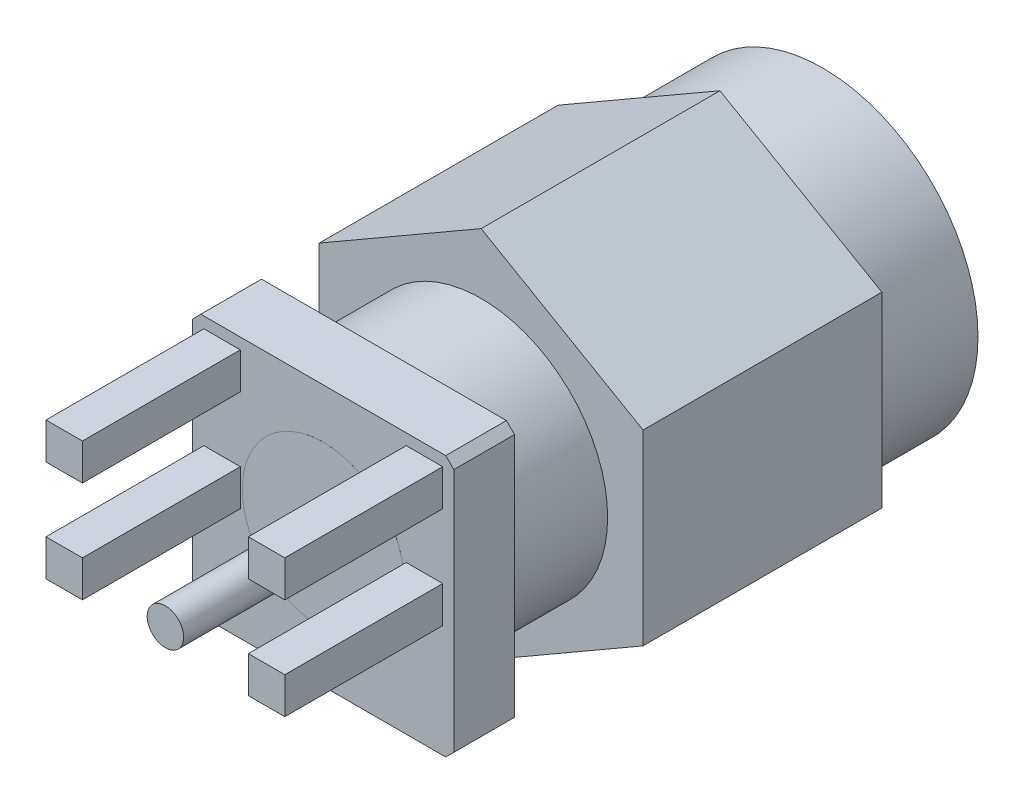
SolidWorks part; units mm, degrees
ref_plane "Спереди" through (0, 0, 0) normal (0, 0, 1) x (1, 0, 0)
ref_plane "Сверху" through (0, 0, 0) normal (0, 1, 0) x (1, 0, 0)
ref_plane "Справа" through (0, 0, 0) normal (1, 0, 0) x (0, 0, -1)
sketch "Эскиз1" plane through (0, 0, 0) normal (0, 0, 1) x (1, 0, 0)
  line L0 (3.225, 2.95) -> (-3.225, 2.95) construction
  line L1 (3.225, -3.225) -> (-3.225, -3.225)
  line L2 (3.225, -3.225) -> (3.225, 3.225)
  line L3 (3.225, 3.225) -> (-3.225, 3.225)
  line L4 (-3.225, -3.225) -> (-3.225, 3.225)
  line L5 (3.225, -3.225) -> (-3.225, 3.225) construction
  line L6 (3.225, 3.225) -> (-3.225, -3.225) construction
  line L7 (-2.95, 3.225) -> (-2.95, -3.225) construction
  line L8 (2.95, 3.225) -> (2.95, -3.225) construction
  line L9 (-2.95, 2.95) -> (-2.05, 2.95)
  line L13 (-3.225, 2.05) -> (3.225, 2.05) construction
  line L14 (-3.225, 0.45) -> (3.225, 0.45) construction
  line L15 (-3.225, -0.45) -> (3.225, -0.45) construction
  line L16 (-2.05, 2.05) -> (-2.95, 2.05)
  line L17 (-2.95, 2.05) -> (-2.95, 2.95)
  line L18 (-2.05, 2.95) -> (-2.05, 2.05)
  line L19 (-2.05, 3.225) -> (-2.05, -3.225) construction
  line L20 (2.95, 2.95) -> (2.05, 2.95)
  line L21 (2.95, 2.95) -> (2.95, 2.05)
  line L22 (2.95, 2.05) -> (2.05, 2.05)
  line L23 (2.05, 2.95) -> (2.05, 2.05)
  line L24 (2.05, 3.225) -> (2.05, -3.225) construction
  line L26 (-2.05, 0.45) -> (-2.95, 0.45)
  line L27 (-2.05, 0.45) -> (-2.05, -0.45)
  line L28 (-2.05, -0.45) -> (-2.95, -0.45)
  line L29 (-2.95, 0.45) -> (-2.95, -0.45)
  line L30 (2.05, 0.45) -> (2.95, 0.45)
  line L31 (2.05, 0.45) -> (2.05, -0.45)
  line L32 (2.05, -0.45) -> (2.95, -0.45)
  line L33 (2.95, 0.45) -> (2.95, -0.45)
  line L34 (0, 4.6188) -> (-4, 2.3094)
  line L35 (-4, 2.3094) -> (-4, -2.3094)
  line L36 (-4, -2.3094) -> (0, -4.6188)
  line L37 (0, -4.6188) -> (4, -2.3094)
  line L38 (4, -2.3094) -> (4, 2.3094)
  line L39 (4, 2.3094) -> (0, 4.6188)
  circle A1 centre (0, 0) radius 0.45
  circle A2 centre (0, 0) radius 3.125
  circle A3 centre (0, 0) radius 4 construction
  circle A4 centre (0, 0) radius 3.835
  circle A5 centre (0, 0) radius 2
  point P0 (0, 0)
  dimension "D6" = 0.9
  dimension "D10" = 6.25
  dimension "D12" = 4
  dimension "D1" = 6.45
  dimension "D2" = 6.45
  dimension "D3" = 0.275
  dimension "D4" = 0.275
  dimension "D5" = 0.275
  dimension "D7" = 0.9
  dimension "D8" = 0.45
  dimension "D9" = 0.9
  dimension "D11" = 8
extrude "Бобышка-Вытянуть1" add sketch "Эскиз1" along normal blind 3.9 contours A2 L18 L9 L34 L17 L16 | A2 L22 L21 L39 L20 L23 | L33 L30 L31 L32 | L26 L29 L28 L27 | L18 A2 L16 | L22 A2 L23 | L34 L9 L17 | L39 L21 L20 | A4 L9 L34 L17 | A4 L21 L39 L20 region at (2.7874, 2.7873, 0) region at (2.4742, 2.4742, 0) region at (2.9302, 2.9385, 0) region at (-2.4742, 2.4742, 0) region at (-2.7874, 2.7873, 0) region at (2.1553, 2.1553, 0) region at (-2.9302, 2.9385, 0) region at (-2.1553, 2.1553, 0) region at (-2.5, 0, 0) region at (2.5, 0, 0)
extrude "Бобышка-Вытянуть2" add sketch "Эскиз1<3>" against normal blind 1.5 contours L3 L4 L1 L2
sketch "Эскиз1<3>" plane through (0, 0, 0) normal (0, 0, 1) x (1, 0, 0) same geometry as "Эскиз1"
extrude "Бобышка-Вытянуть3" add sketch "Эскиз1<4>" against normal blind 3.9 contours A2
sketch "Эскиз1<4>" plane through (0, 0, 0) normal (0, 0, 1) x (1, 0, 0) same geometry as "Эскиз1"
extrude "Бобышка-Вытянуть4" add sketch "Эскиз1<5>" against normal blind 5.9 from surface contours L34 L35 L36 L37 L38 L39 starting at face at (3.125, 0, -3.9)
sketch "Эскиз1<5>" plane through (0, 0, 0) normal (0, 0, 1) x (1, 0, 0) same geometry as "Эскиз1"
extrude "Бобышка-Вытянуть5" add sketch "Эскиз1<6>" against normal blind 2.54 from surface contours A4 starting at face at (0, 0, -9.8)
sketch "Эскиз1<6>" plane through (0, 0, 0) normal (0, 0, 1) x (1, 0, 0) same geometry as "Эскиз1"
sketch "Эскиз2" plane through (0, 0, -12.34) normal (0, 0, -1) x (-1, 0, 0)
  circle A0 centre (0, 0) radius 3.335
extrude "Вырез-Вытянуть1" cut sketch "Эскиз2" against normal blind 6
extrude "Вырез-Вытянуть2" cut sketch "Эскиз1<7>" against normal blind 9 contours A5 A1 region at (-1.9434, 0, 0)
sketch "Эскиз1<7>" plane through (0, 0, 0) normal (0, 0, 1) x (1, 0, 0) same geometry as "Эскиз1"
extrude "Бобышка-Вытянуть6" add sketch "Эскиз1<8>" along normal blind 3.9 and the other way blind 12 contours A1 region at (0, 0, 0)
sketch "Эскиз1<8>" plane through (0, 0, 0) normal (0, 0, 1) x (1, 0, 0) same geometry as "Эскиз1"
extrude "Бобышка-Вытянуть7" add sketch "Эскиз1<9>" against normal blind 8.4 and the other way blind 0.0004 contours A5 A1 region at (-1.9434, 0, 0)
sketch "Эскиз1<9>" plane through (0, 0, 0) normal (0, 0, 1) x (1, 0, 0) same geometry as "Эскиз1"
thread "Резьба1" pitch 0.8 method extrude profile "Профиль резьбы1" start angle 0, offset 0, length 0, pitch 0.8, diameter 6.67
ref_plane "Плоскость1" through (3.335, 0, -12.34) normal (0, -1, 0) x (1, 0, 0)
sketch "Профиль резьбы1" plane through (3.335, 0, -12.34) normal (0, -1, 0) x (1, 0, 0)
  line L0 (0, 0) -> (0, 0.8) construction
  line L11 (0, 0) -> (0, 0.7)
  line L12 (0, 0.7) -> (-0.433, 0.45)
  line L13 (-0.433, 0.45) -> (-0.433, 0.25)
  line L15 (-0.433, 0.25) -> (0, 0)
  line L17 (-0.433, 0.35) -> (0, 0.35) construction
  point P2 (0, 0)
  dimension "Pitch" = 0.8
  dimension "Profile_Angle" = 60
  dimension "Profile_Land" = 0.2
  dimension "Profile_Height" = 0.433
fillet "Скругление1" radius 0.35 1 edges at (0.45, 0, -12) conic radius 0.5
chamfer "Фаска1" distance 0.2 angle 45 4 edges at (3.225, 3.225, -0.75) (3.225, -3.225, -0.75) (-3.225, -3.225, -0.75) (-3.225, 3.225, -0.75)
